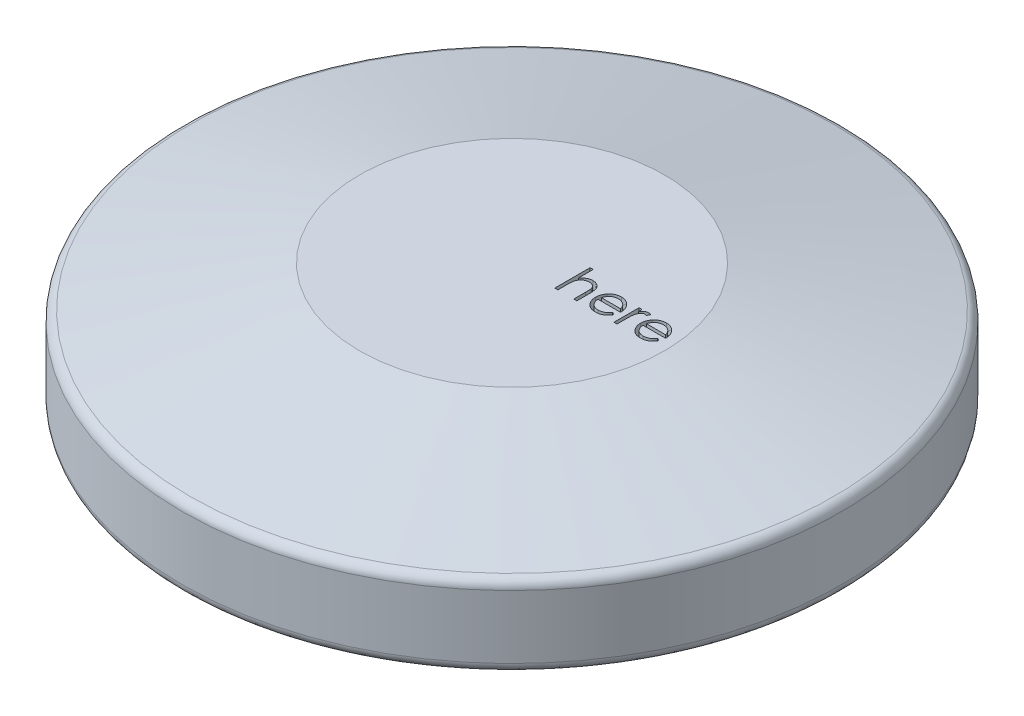
SolidWorks part; units mm, degrees
ref_plane "Front Plane" through (0, 0, 0) normal (0, 0, 1) x (1, 0, 0)
ref_plane "Top Plane" through (0, 0, 0) normal (0, 1, 0) x (1, 0, 0)
ref_plane "Right Plane" through (0, 0, 0) normal (1, 0, 0) x (0, 0, -1)
sketch "Sketch1" plane through (0, 0, 0) normal (0, 1, 0) x (1, 0, 0)
  circle A0 centre (0, 0) radius 33.5
  circle A1 centre (0, 0) radius 15.5
extrude "Boss-Extrude1" add sketch "Sketch1" along normal blind 4 and the other way blind 4
extrude "Boss-Extrude2" add sketch "Sketch1<2>" along normal blind 8.375 and the other way blind 8.375 contours A1
sketch "Sketch1<2>" plane through (0, 0, 0) normal (0, 1, 0) x (1, 0, 0) same geometry as "Sketch1"
loft "Loft1" add section edge at (0, 4, 33.5) section edge at (0, 8.375, 15.5) connector at (32.8082, 4, -6.7728) connector at (14.8004, 8.375, -4.6041)
loft "Loft2" add section edge at (0, -8.375, 15.5) section edge at (0, -4, 33.5) connector at (15.1414, -8.375, 3.3147) connector at (33.4996, -4, -0.1684)
fillet "Fillet1" radius 1 1 edges at (0, 4, 33.5)
fillet "Fillet2" radius 1 1 edges at (0, -4, 33.5)
sketch "Sketch2" plane through (0, 8.375, 0) normal (0, 1, 0) x (1, 0, 0)
  text T1 "here\r\n"
extrude "Cut-Extrude1" cut sketch "Sketch2" against normal blind 1
